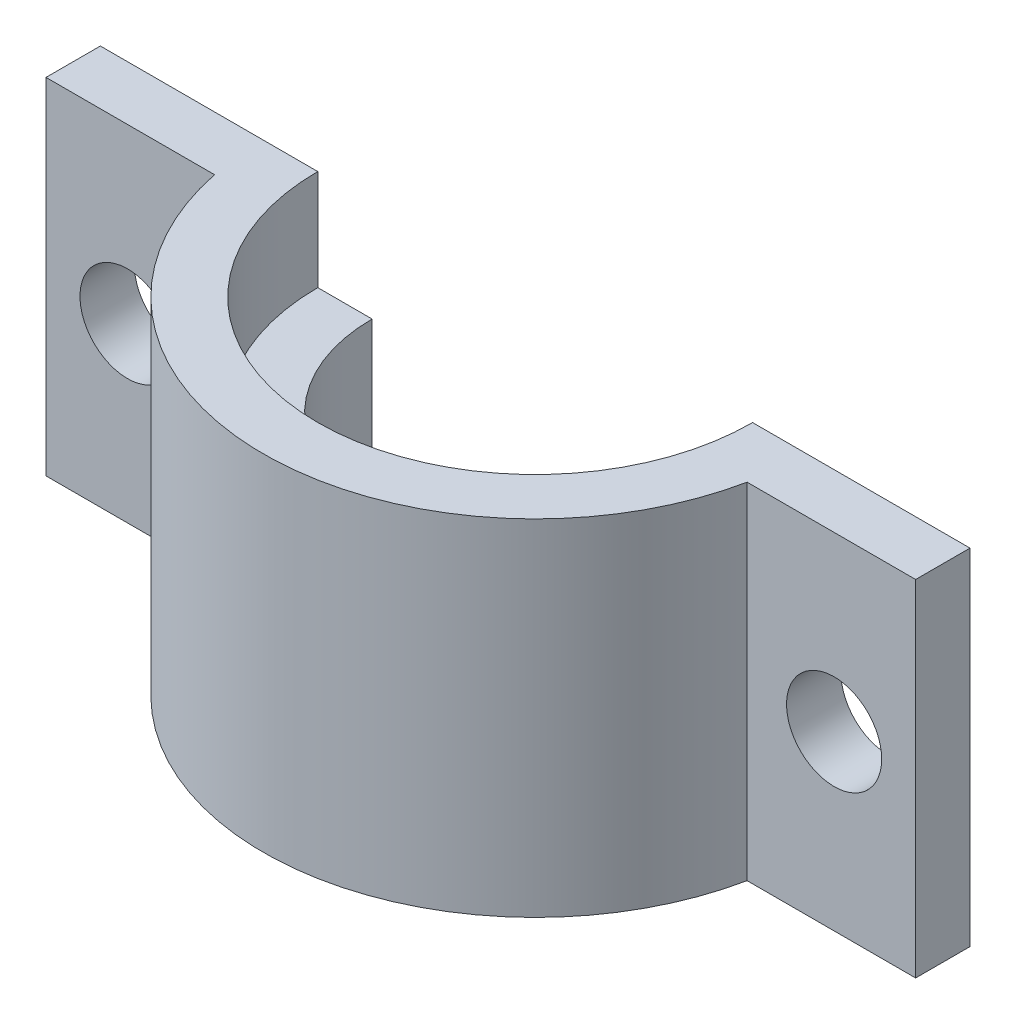
SolidWorks part; units mm, degrees
ref_plane "Front Plane" through (0, 0, 0) normal (0, 0, 1) x (1, 0, 0)
ref_plane "Top Plane" through (0, 0, 0) normal (0, 1, 0) x (1, 0, 0)
ref_plane "Right Plane" through (0, 0, 0) normal (1, 0, 0) x (0, 0, -1)
sketch "Sketch1" plane through (0, 0, 0) normal (0, 0, 1) x (1, 0, 0)
  line L1 (-16, 6.35) -> (16, 6.35)
  line L2 (-16, 6.35) -> (-16, -6.35)
  line L3 (-16, -6.35) -> (16, -6.35)
  line L4 (16, 6.35) -> (16, -6.35)
  line L5 (-16, 6.35) -> (16, -6.35) construction
  line L6 (-16, -6.35) -> (16, 6.35) construction
  point P0 (0, 0)
  dimension "D1" = 32
  dimension "D2" = 12.7
extrude "Boss-Extrude1" add sketch "Sketch1" along normal blind 12
sketch "Sketch3" plane through (0, 0, 0) normal (1, 0, 0) x (0, 0, -1)
  line L0 (0, 6.35) -> (-8, 6.35)
  line L1 (0, 6.35) -> (0, -6.35)
  line L2 (-12, 6.35) -> (0, 6.35) construction
  line L3 (-8, 6.35) -> (-8, 2.65)
  line L4 (-8, 2.65) -> (-6, 2.65)
  line L5 (-6, 2.65) -> (-6, -3.35)
  line L6 (-6, -3.35) -> (-8, -3.35)
  line L7 (-8, -3.35) -> (-8, -6.35)
  line L8 (-8, -6.35) -> (0, -6.35)
  line L9 (-12, -6.35) -> (0, -6.35) construction
  line L11 (0, -6.35) -> (0, 6.35) construction
  dimension "D1" = 8
  dimension "D2" = 6
  dimension "D3" = 3.7
  dimension "D4" = 3
revolve "Cut-Revolve1" cut sketch "Sketch3" angle 360 about L1
sketch "Sketch4" plane through (0, 6.35, 0) normal (0, 1, 0) x (1, 0, 0)
  line L0 (-16, -2) -> (-9.798, -2)
  line L1 (-16, -12) -> (-16, 0) construction
  line L2 (9.798, -2) -> (16, -2)
  line L3 (16, -12) -> (16, 0) construction
  line L7 (-16, -2) -> (-16, -15)
  line L8 (-16, -15) -> (16, -15)
  line L9 (16, -15) -> (16, -2)
  line L10 (-8, 0) -> (-16, 0) construction
  line L11 (16, -12) -> (-16, -12) construction
  arc A0 (-9.798, -2) -> (9.798, -2) centre (0, 0) ccw
  dimension "D1" = 20
  dimension "D2" = 2
  dimension "D3" = 3
extrude "Cut-Extrude1" cut sketch "Sketch4" against normal through all
sketch "Sketch5" plane through (0, 0, 2) normal (0, 0, 1) x (1, 0, 0)
  line L0 (-16, 0) -> (-10, 0) construction
  line L1 (-16, -6.35) -> (-16, 6.35) construction
  line L2 (16, 0) -> (10, 0) construction
  line L3 (16, -6.35) -> (16, 6.35) construction
  circle A0 centre (-13, 0) radius 1.75
  circle A1 centre (13, 0) radius 1.75
  dimension "D3" = 3.5
  dimension "D4" = 3.5
  dimension "D1" = 6
  dimension "D2" = 6
extrude "Cut-Extrude2" cut sketch "Sketch5" against normal through all
